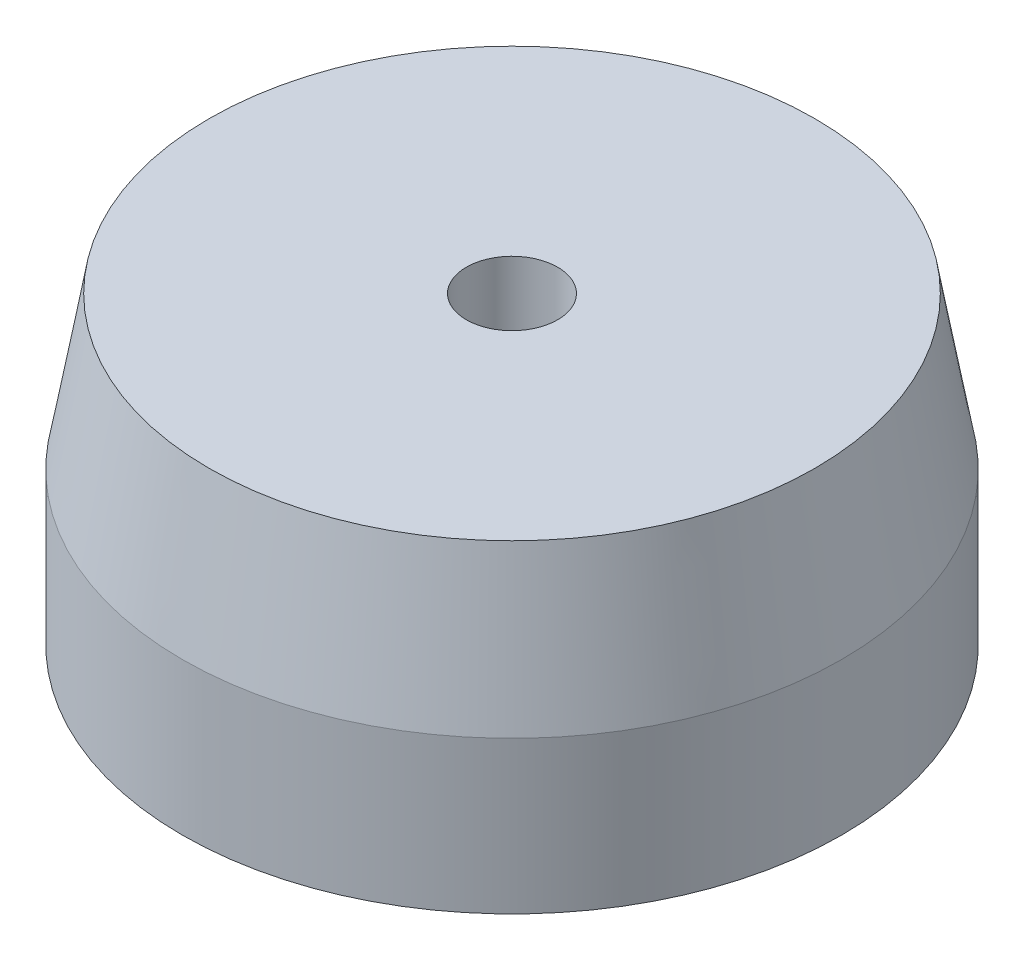
SolidWorks part; units mm, degrees
ref_plane "Front Plane" through (0, 0, 0) normal (0, 0, 1) x (1, 0, 0)
ref_plane "Top Plane" through (0, 0, 0) normal (0, 1, 0) x (1, 0, 0)
ref_plane "Right Plane" through (0, 0, 0) normal (1, 0, 0) x (0, 0, -1)
sketch "Sketch1" plane through (0, 0, 0) normal (0, 1, 0) x (1, 0, 0)
  circle A0 centre (0, 0) radius 13.25 construction
  circle A1 centre (0, 0) radius 1.5
  circle A2 centre (0, 0) radius 10.837
  dimension "D1" = 26.5
  dimension "D2" = 2.413
  dimension "D3" = 3
extrude "Boss-Extrude1" add sketch "Sketch1" along normal blind 10
chamfer "Chamfer1" distance 5 angle 10 1 edges at (0, 10, 10.837) first distance on face at (0, 10, 10.837)
